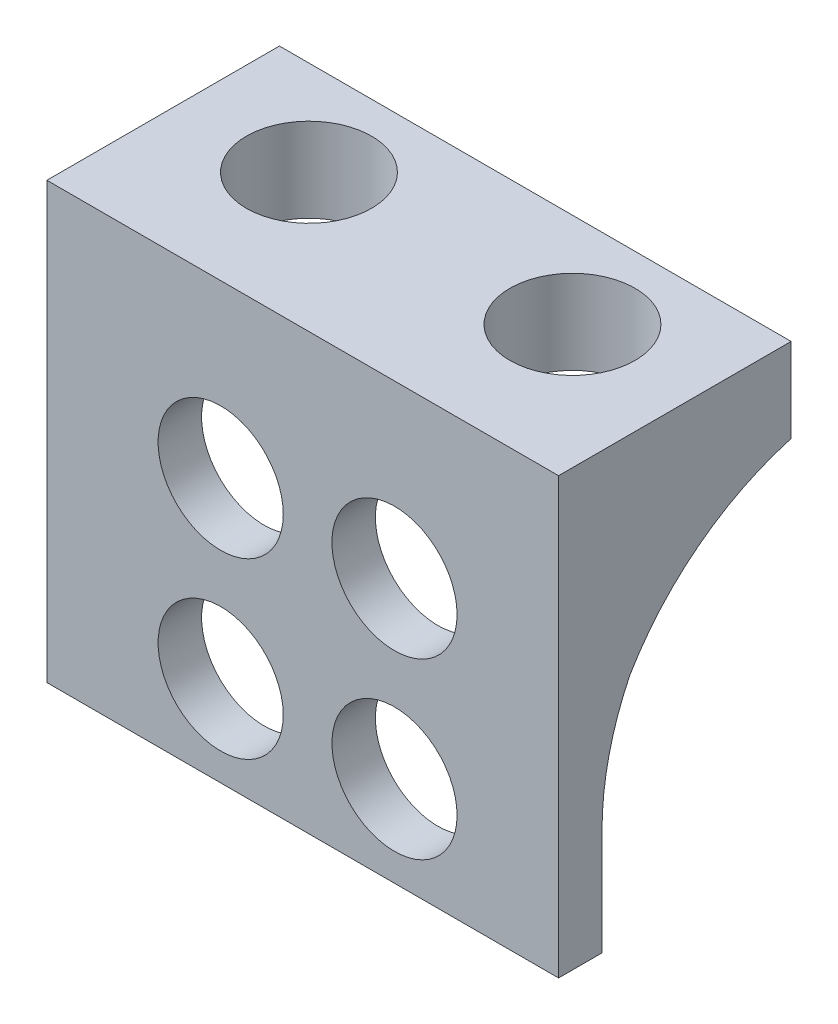
SolidWorks part; units mm, degrees
ref_plane "Front Plane" through (0, 0, 0) normal (0, 0, 1) x (1, 0, 0)
ref_plane "Top Plane" through (0, 0, 0) normal (0, 1, 0) x (1, 0, 0)
ref_plane "Right Plane" through (0, 0, 0) normal (1, 0, 0) x (0, 0, -1)
sketch "Sketch1" plane through (0, 0, 0) normal (0, 1, 0) x (1, 0, 0)
  line L1 (0, 0) -> (18.6944, 0)
  line L2 (0, 0) -> (0, -6.9088)
  line L3 (0, -6.9088) -> (18.6944, -6.9088)
  line L4 (18.6944, 0) -> (18.6944, -6.9088)
  dimension "D1" = 18.6944
  dimension "D2" = 6.9088
extrude "Boss-Extrude1" add sketch "Sketch1" along normal blind 3.0734
sketch "Sketch2" plane through (0, 3.0734, 0) normal (0, 1, 0) x (1, 0, 0)
  line L0 (0, 0) -> (0, -6.9088) construction
  line L1 (0, -3.4544) -> (4.5339, -3.4544)
  line L2 (9.3472, 0) -> (9.3472, -6.9088)
  line L3 (18.6944, 0) -> (0, 0) construction
  line L4 (0, -6.9088) -> (18.6944, -6.9088) construction
  circle A0 centre (4.5339, -3.4544) radius 2.286
  circle A1 centre (14.1605, -3.4544) radius 2.286
extrude "Cut-Extrude1" cut sketch "Sketch2" against normal blind 3.0734
sketch "Sketch3" plane through (0, 0, 6.9088) normal (0, 0, 1) x (1, 0, 0)
  line L0 (18.6944, 3.0734) -> (18.6944, 0) construction
  line L1 (0, 3.0734) -> (18.6944, 3.0734)
  line L2 (0, 3.0734) -> (0, 0)
  line L3 (0, 0) -> (18.6944, 0)
  line L4 (18.6944, 3.0734) -> (18.6944, 0)
  line L5 (0, 0) -> (18.6944, 0) construction
  line L6 (6.35, -3.175) -> (12.7, -3.175)
  line L7 (0, 3.0734) -> (18.6944, 3.0734)
  line L8 (0, 3.0734) -> (0, -9.6266)
  line L9 (0, -9.6266) -> (18.6944, -9.6266)
  line L10 (18.6944, 3.0734) -> (18.6944, -9.6266)
  line L11 (0, 0) -> (6.35, 0)
  line L12 (0, 0) -> (0, -6.35)
  line L13 (0, -6.35) -> (6.35, -6.35)
  line L14 (6.35, 0) -> (6.35, -6.35)
  line L15 (6.35, -6.35) -> (18.6944, -6.35)
  line L16 (6.35, -11.811) -> (6.35, -12.8197)
  line L17 (6.35, -12.8197) -> (0, -12.8197)
  line L18 (0, -12.8197) -> (0, -9.6266)
  line L19 (0, -12.8197) -> (18.6944, -12.8197)
  line L20 (18.6944, -12.8197) -> (18.6944, -9.6266)
  circle A0 centre (6.35, -3.175) radius 2.286
  circle A1 centre (12.7, -3.175) radius 2.286
  circle A2 centre (12.7, -9.525) radius 2.286
  circle A3 centre (6.35, -9.525) radius 2.286
extrude "Boss-Extrude3" add sketch "Sketch3" along normal blind 1.5875
sketch "Sketch4" plane through (0, 0, 0) normal (-1, 0, 0) x (0, 0, 1)
  line L0 (3.4544, 0) -> (6.9088, -6.4099)
  line L1 (0, 0) -> (6.9088, 0) construction
  line L2 (6.9088, 0) -> (6.9088, -12.8197) construction
  line L3 (6.9088, -6.4099) -> (6.9088, 0)
  line L4 (6.9088, 0) -> (3.4544, 0)
extrude "Boss-Extrude4" add sketch "Sketch4" against normal blind 1.5875
sketch "Sketch5" plane through (18.6944, 0, 0) normal (1, 0, 0) x (0, 0, -1)
  line L0 (-3.4544, 0) -> (-6.9088, -6.4099)
  line L1 (-6.9088, 0) -> (0, 0) construction
  line L2 (-6.9088, 0) -> (-6.9088, -12.8197) construction
  line L3 (-6.9088, -6.4099) -> (-6.9088, 0)
  line L4 (-6.9088, 0) -> (-3.4544, 0)
extrude "Boss-Extrude5" add sketch "Sketch5" against normal blind 1.5875
fillet "Fillet1" radius 10 4 edges at (0.7938, -6.4099, 6.9088) (0.7938, 0, 3.4544) (17.9007, 0, 3.4544) (17.9007, -6.4099, 6.9088)
